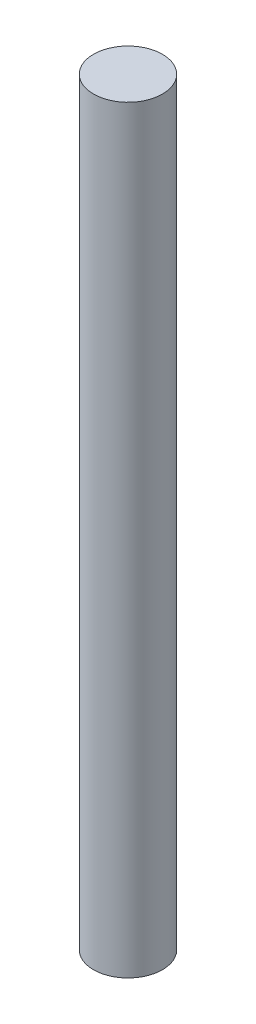
SolidWorks part; units mm, degrees
ref_plane "Front Plane" through (0, 0, 0) normal (0, 0, 1) x (1, 0, 0)
ref_plane "Top Plane" through (0, 0, 0) normal (0, 1, 0) x (1, 0, 0)
ref_plane "Right Plane" through (0, 0, 0) normal (1, 0, 0) x (0, 0, -1)
sketch "Sketch1" plane through (0, 0, 0) normal (0, 1, 0) x (1, 0, 0)
  circle A0 centre (0, 0) radius 1.5
  dimension "D1" = 3
extrude "Boss-Extrude1" add sketch "Sketch1" along normal blind 33
